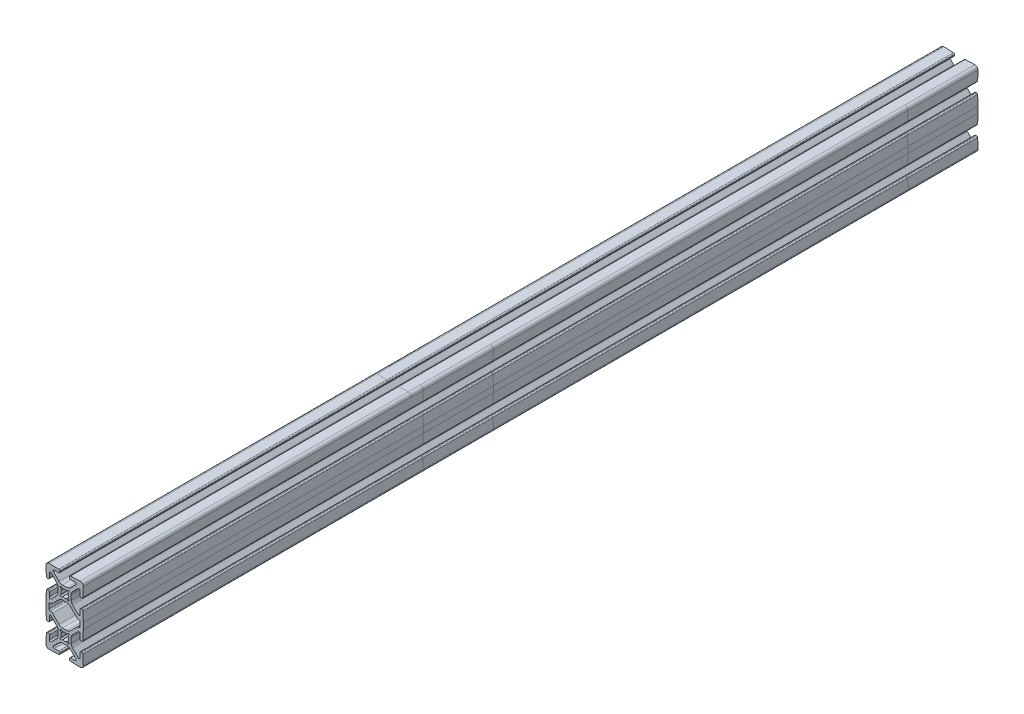
SolidWorks part; units mm, degrees
ref_plane "Front Plane" through (0, 0, 0) normal (0, 0, 1) x (1, 0, 0)
ref_plane "Top Plane" through (0, 0, 0) normal (0, 1, 0) x (1, 0, 0)
ref_plane "Right Plane" through (0, 0, 0) normal (1, 0, 0) x (0, 0, -1)
sketch "Sketch1" plane through (0, 0, 0) normal (0, 0, 1) x (1, 0, 0)
  line L0 (0, 12.5) -> (0, 25) construction
  line L1 (0, 12.5) -> (12.5, 12.5) construction
  line L2 (0, 12.5) -> (-12.5, 25) construction
  line L3 (-10.3971, 24.9988) -> (-3.9863, 24.7749)
  line L4 (-12.5, 25) -> (0, 25) construction
  line L5 (-3.2505, 23.9858) -> (-3.2689, 23.4569)
  line L6 (-4.058, 22.7211) -> (-6.948, 22.8221)
  line L10 (0, 16.88) -> (-1.5587, 16.88)
  line L11 (-3.8038, 17.8099) -> (-7.5141, 21.5202)
  line L24 (0, 12.5) -> (-12.5, 12.5) construction
  line L25 (-12.5, 12.5) -> (0, 12.5) construction
  line L26 (0, 12.5) -> (0, 0) construction
  line L27 (-12.5, 0) -> (-12.5, 25) construction
  line L28 (0, 25) -> (12.5, 25) construction
  line L29 (0, 0) -> (0, -25) construction
  line L30 (-12.5, -25) -> (12.5, -25) construction
  arc A0 (-11.9048, 24.4048) -> (-10.3971, 24.9988) centre (-10.468, 22.968) cw
  arc A4 (-3.2689, 23.4569) -> (-4.058, 22.7211) centre (-4.0314, 23.4836) cw
  arc A5 (-3.9863, 24.7749) -> (-3.2505, 23.9858) centre (-4.0129, 24.0125) cw
  arc A6 (-1.5587, 16.88) -> (-3.8038, 17.8099) centre (-1.5587, 20.055) cw
  circle A16 centre (0, 12.5) radius 2.55
  arc A18 (-7.5141, 21.5202) -> (-6.948, 22.8221) centre (-6.9746, 22.0596) cw
  circle A19 centre (-2.3794, 14.8794) radius 0.635 construction
  point P15 (0, 0)
  point P35 (-3.2956, 22.6945)
  point P38 (-3.2238, 24.7483)
  point P42 (-2.8739, 16.88)
  point P80 (-12.5, 12.5)
  point P85 (0, 0)
  point P88 (0, 0)
  dimension "D11" = 2.032
  dimension "D15" = 3.175
  dimension "Center Hole Diameter" = 5.1
  dimension "D6" = 1.27
  dimension "D1" = 45
  dimension "D2" = 2
  dimension "Rail Width" = 25
  dimension "D10" = 2.13
  dimension "T-Slot Depth" = 8.12
  dimension "D9" = 2.055
  dimension "Rail Height" = 50
  dimension "D23" = 8.76
  dimension "D5" = 15.475
  dimension "T-Slot Width" = 6.5
  dimension "D3" = 4
sketch "Sketch2" plane through (0, 0, 0) normal (1, 0, 0) x (0, 0, -1)
  line L0 (-300, 0) -> (300, 0)
  line L1 (-300, -25) -> (-300, 25) construction
  line L2 (0, 12.5) -> (0, 25) construction
  line L3 (0, 12.5) -> (0, 25) construction
  line L4 (300, -25) -> (300, 25) construction
  point P0 (-262.5, 0)
  point P3 (0, 0)
  point P7 (262.5, 0)
  point P11 (-300, 0)
  dimension "D1" = 37.5
  dimension "Representative Length" = 600
sketch "Sketch3" plane through (0, 0, 0) normal (0, 0, 1) x (1, 0, 0)
  line L1 (0, 12.5) -> (-12.5, 25) construction
  line L2 (0, 12.5) -> (-12.5, 25) construction
  line L3 (-4.38, 12.5) -> (-2.55, 12.5) construction
  line L4 (-4.38, 10.9413) -> (-4.38, 14.0587)
  line L5 (-10.3971, 24.9988) -> (-3.9863, 24.7749) construction
  line L6 (-3.2505, 23.9858) -> (-3.2689, 23.4569) construction
  line L7 (-4.058, 22.7211) -> (-6.948, 22.8221) construction
  line L12 (-5.3099, 16.3038) -> (-9.0202, 20.0141)
  line L13 (-10.2211, 16.558) -> (-10.3221, 19.448)
  line L14 (-11.4858, 15.7505) -> (-10.9569, 15.7689)
  line L15 (-12.4988, 22.8971) -> (-12.2749, 16.4863)
  line L16 (-2.8284, 14.4304) -> (-2.1953, 13.7973)
  line L17 (1.5587, 8.12) -> (-1.5587, 8.12)
  line L18 (-1.2973, 14.6953) -> (-1.9304, 15.3284)
  line L19 (-3.8038, 7.1901) -> (-8.1307, 2.8632)
  line L23 (-1.2973, 10.3047) -> (-1.9304, 9.6716)
  line L42 (-3.8038, 17.8099) -> (-7.5141, 21.5202) construction
  line L43 (0, 16.88) -> (-1.5587, 16.88) construction
  line L44 (-10.3971, 24.9988) -> (-3.9863, 24.7749)
  line L45 (-3.2505, 23.9858) -> (-3.2689, 23.4569)
  line L46 (-4.058, 22.7211) -> (-6.948, 22.8221)
  line L47 (-3.8038, 17.8099) -> (-7.5141, 21.5202)
  line L48 (1.5587, 16.88) -> (-1.5587, 16.88)
  line L59 (0, 16.88) -> (0, 15.05) construction
  line L60 (-2.8284, 10.5696) -> (-2.1953, 11.2027)
  line L61 (-12.5, 2.0675) -> (-12.2749, 8.5137)
  line L62 (-11.4858, 9.2495) -> (-10.9569, 9.2311)
  line L63 (-10.2211, 8.442) -> (-10.3221, 5.552)
  line L64 (-5.3099, 8.6962) -> (-9.0202, 4.9859)
  line L66 (10.468, 0) -> (-10.468, 0) construction
  line L67 (-10.468, 0) -> (-10.468, 1.506)
  line L68 (-9.706, 2.268) -> (-9.5675, 2.268)
  line L71 (-12.5, 0) -> (-12.5, 2.0675)
  line L72 (-12.5, 0) -> (-12.5, 25) construction
  line L76 (-12.5, 0) -> (-10.468, 0)
  line L78 (4.38, 12.5) -> (2.55, 12.5) construction
  line L79 (12.5, 0) -> (10.468, 0)
  line L80 (12.5, 0) -> (12.5, 2.0675)
  line L81 (9.706, 2.268) -> (9.5675, 2.268)
  line L82 (10.468, 0) -> (10.468, 1.506)
  line L83 (5.3099, 8.6962) -> (9.0202, 4.9859)
  line L84 (10.2211, 8.442) -> (10.3221, 5.552)
  line L85 (11.4858, 9.2495) -> (10.9569, 9.2311)
  line L86 (12.5, 2.0675) -> (12.2749, 8.5137)
  line L87 (2.8284, 10.5696) -> (2.1953, 11.2027)
  line L89 (3.8038, 17.8099) -> (7.5141, 21.5202)
  line L90 (4.058, 22.7211) -> (6.948, 22.8221)
  line L91 (3.2505, 23.9858) -> (3.2689, 23.4569)
  line L92 (10.3971, 24.9988) -> (3.9863, 24.7749)
  line L93 (1.2973, 10.3047) -> (1.9304, 9.6716)
  line L94 (3.8038, 7.1901) -> (8.1307, 2.8632)
  line L95 (1.2973, 14.6953) -> (1.9304, 15.3284)
  line L97 (2.8284, 14.4304) -> (2.1953, 13.7973)
  line L98 (12.4988, 22.8971) -> (12.2749, 16.4863)
  line L99 (11.4858, 15.7505) -> (10.9569, 15.7689)
  line L100 (10.2211, 16.558) -> (10.3221, 19.448)
  line L101 (5.3099, 16.3038) -> (9.0202, 20.0141)
  line L102 (4.38, 10.9413) -> (4.38, 14.0587)
  line L103 (0, 12.5) -> (0, 25) construction
  arc A0 (-10.3971, 24.9988) -> (-11.9048, 24.4048) centre (-10.468, 22.968) ccw construction
  arc A1 (-3.8038, 7.1901) -> (-1.5587, 8.12) centre (-1.5587, 4.945) cw
  circle A3 centre (0, 12.5) radius 2.55
  arc A5 (-10.3971, 24.9988) -> (-12.4988, 22.8971) centre (-10.468, 22.968) ccw
  arc A6 (-5.3099, 16.3038) -> (-4.38, 14.0587) centre (-7.555, 14.0587) cw
  arc A7 (-10.3221, 19.448) -> (-9.0202, 20.0141) centre (-9.5596, 19.4746) cw
  arc A8 (-10.2211, 16.558) -> (-10.9569, 15.7689) centre (-10.9836, 16.5314) cw
  arc A9 (-11.4858, 15.7505) -> (-12.2749, 16.4863) centre (-11.5125, 16.5129) cw
  circle A10 centre (-2.3794, 14.8794) radius 0.635 construction
  arc A11 (-1.9304, 15.3284) -> (-2.8284, 14.4304) centre (-2.3794, 14.8794) ccw
  arc A12 (-2.1953, 13.7973) -> (-2.1953, 11.2027) centre (0, 12.5) ccw
  arc A16 (1.2973, 10.3047) -> (-1.2973, 10.3047) centre (0, 12.5) cw
  arc A17 (-1.9304, 9.6716) -> (-2.8284, 10.5696) centre (-2.3794, 10.1206) cw
  arc A18 (-11.4858, 9.2495) -> (-12.2749, 8.5137) centre (-11.5125, 8.4871) ccw
  arc A35 (1.2973, 14.6953) -> (-1.2973, 14.6953) centre (0, 12.5) ccw
  arc A36 (-3.2505, 23.9858) -> (-3.9863, 24.7749) centre (-4.0129, 24.0125) ccw construction
  arc A37 (-4.058, 22.7211) -> (-3.2689, 23.4569) centre (-4.0314, 23.4836) ccw construction
  arc A38 (-6.948, 22.8221) -> (-7.5141, 21.5202) centre (-6.9746, 22.0596) ccw construction
  arc A39 (-3.8038, 17.8099) -> (-1.5587, 16.88) centre (-1.5587, 20.055) ccw construction
  arc A41 (-3.2505, 23.9858) -> (-3.9863, 24.7749) centre (-4.0129, 24.0125) ccw
  arc A42 (-4.058, 22.7211) -> (-3.2689, 23.4569) centre (-4.0314, 23.4836) ccw
  arc A43 (-6.948, 22.8221) -> (-7.5141, 21.5202) centre (-6.9746, 22.0596) ccw
  arc A44 (-3.8038, 17.8099) -> (-1.5587, 16.88) centre (-1.5587, 20.055) ccw
  arc A52 (-10.2211, 8.442) -> (-10.9569, 9.2311) centre (-10.9836, 8.4686) ccw
  arc A53 (-10.3221, 5.552) -> (-9.0202, 4.9859) centre (-9.5596, 5.5254) ccw
  arc A54 (-5.3099, 8.6962) -> (-4.38, 10.9413) centre (-7.555, 10.9413) ccw
  arc A55 (-10.468, 1.506) -> (-9.706, 2.268) centre (-9.706, 1.506) cw
  arc A56 (-9.5675, 2.268) -> (-8.1307, 2.8632) centre (-9.5675, 4.3) ccw
  circle A57 centre (0, 12.5) radius 2.55 construction
  arc A58 (9.5675, 2.268) -> (8.1307, 2.8632) centre (9.5675, 4.3) cw
  arc A59 (10.468, 1.506) -> (9.706, 2.268) centre (9.706, 1.506) ccw
  arc A60 (5.3099, 8.6962) -> (4.38, 10.9413) centre (7.555, 10.9413) cw
  arc A61 (10.3221, 5.552) -> (9.0202, 4.9859) centre (9.5596, 5.5254) cw
  arc A62 (10.2211, 8.442) -> (10.9569, 9.2311) centre (10.9836, 8.4686) cw
  arc A63 (3.8038, 17.8099) -> (1.5587, 16.88) centre (1.5587, 20.055) cw
  arc A64 (6.948, 22.8221) -> (7.5141, 21.5202) centre (6.9746, 22.0596) cw
  arc A65 (4.058, 22.7211) -> (3.2689, 23.4569) centre (4.0314, 23.4836) cw
  arc A66 (3.2505, 23.9858) -> (3.9863, 24.7749) centre (4.0129, 24.0125) cw
  arc A68 (11.4858, 9.2495) -> (12.2749, 8.5137) centre (11.5125, 8.4871) cw
  arc A69 (1.9304, 9.6716) -> (2.8284, 10.5696) centre (2.3794, 10.1206) ccw
  arc A71 (2.1953, 13.7973) -> (2.1953, 11.2027) centre (0, 12.5) cw
  arc A72 (1.9304, 15.3284) -> (2.8284, 14.4304) centre (2.3794, 14.8794) cw
  arc A73 (11.4858, 15.7505) -> (12.2749, 16.4863) centre (11.5125, 16.5129) ccw
  arc A74 (10.2211, 16.558) -> (10.9569, 15.7689) centre (10.9836, 16.5314) ccw
  arc A75 (10.3221, 19.448) -> (9.0202, 20.0141) centre (9.5596, 19.4746) ccw
  arc A76 (5.3099, 16.3038) -> (4.38, 14.0587) centre (7.555, 14.0587) ccw
  arc A77 (10.3971, 24.9988) -> (12.4988, 22.8971) centre (10.468, 22.968) cw
  arc A78 (3.8038, 7.1901) -> (1.5587, 8.12) centre (1.5587, 4.945) ccw
  point P40 (0, 0)
  dimension "D3" = 2.032
  dimension "D4" = 0.762
  dimension "D5" = 2.032
  dimension "D2" = 4.536
  dimension "D1" = 0
extrude "Boss-Extrude1" add sketch "Sketch3" along normal mid plane 600
pattern_circular "CirPattern1" count 2 over 360 about axis through (0, 0, 300) along (0, 0, -1) of "Boss-Extrude1"
ref_plane "Contact Plane 1" through (0, 25, 0) normal (0, 1, 0) x (1, 0, 0)
ref_plane "Contact Plane 2" through (12.5, 12.5, 0) normal (1, 0, 0) x (0, 0, -1)
ref_plane "Contact Plane 3" through (0, -25, 0) normal (0, -1, 0) x (-1, 0, 0)
ref_plane "Contact Plane 4" through (-12.5, 12.5, 0) normal (-1, 0, 0) x (0, 0, 1)
sketch "Sketch4" plane through (140, 24.7749, 190) normal (0, 1, 0) x (1, 0, 0)
  line L0 (-127.5012, -110) -> (-127.5012, 490) construction
  line L1 (-152.5, -110) -> (-127.5012, -110)
  line L2 (-152.5, -110) -> (-152.5, 110)
  line L3 (-152.5, 110) -> (-127.5012, 110)
  line L4 (-127.5012, -110) -> (-127.5012, 110)
  dimension "D1" = 220
split line "Split Line1"
sketch "Sketch5" plane through (140, 24.7749, 190) normal (1, 0, 0) x (0, -1, 0)
  line L0 (49.7737, -110) -> (49.7737, 490) construction
  line L1 (-0.2251, 490) -> (49.7737, 490)
  line L2 (-0.2251, 490) -> (-0.2251, 443)
  line L3 (-0.2251, 443) -> (49.7737, 443)
  line L4 (49.7737, 490) -> (49.7737, 443)
  line L5 (-0.2251, 490) -> (-0.2251, 110) construction
  line L6 (-0.2251, 165) -> (49.7749, 165)
  line L7 (-0.2251, 165) -> (-0.2251, 118)
  line L8 (-0.2251, 118) -> (49.7749, 118)
  line L9 (49.7749, 165) -> (49.7749, 118)
  line L10 (49.7749, -110) -> (49.7749, 490) construction
  dimension "D1" = 47
  dimension "D2" = 47
  dimension "D3" = 325
split line "Split Line2"
sketch "Sketch6" plane through (140, 24.7749, 190) normal (0, 1, 0) x (1, 0, 0)
  line L0 (-127.5012, -110) -> (-127.5012, 110) construction
  line L1 (-152.5, 490) -> (-127.5012, 490)
  line L2 (-152.5, 490) -> (-152.5, 89)
  line L3 (-152.5, 89) -> (-127.5012, 89)
  line L4 (-127.5012, 490) -> (-127.5012, 89)
  line L5 (-373.7, 89) -> (388.3, 89) construction
split line "Split Line3"
split line "Split Line4"
sketch "Sketch5<2>" plane through (140, 24.7749, 190) normal (1, 0, 0) x (0, -1, 0) same geometry as "Sketch5"
equation "\"D1@Sketch2\"=\"Rail Width@Sketch1\"*1.5"
equation "\"D1@Boss-Extrude1\" = \"Representative Length@Sketch2\""
